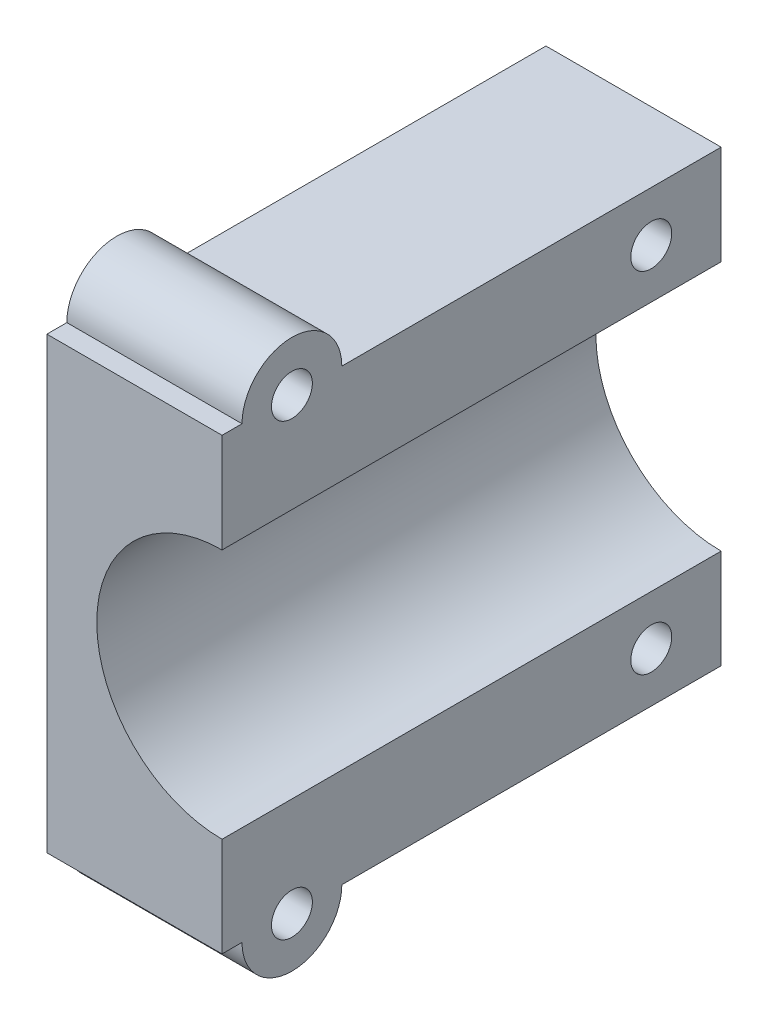
SolidWorks part; units mm, degrees
material "PLA"
ref_plane "Front Plane" through (0, 0, 0) normal (0, 0, 1) x (1, 0, 0)
ref_plane "Top Plane" through (0, 0, 0) normal (0, 1, 0) x (1, 0, 0)
ref_plane "Right Plane" through (0, 0, 0) normal (1, 0, 0) x (0, 0, -1)
sketch "Sketch1" plane through (0, 0, 0) normal (0, 0, 1) x (1, 0, 0)
  line L0 (-17.55, 22.5) -> (-17.55, 0)
  line L1 (55, 0) -> (-55, 0) construction
  line L2 (-17.55, 0) -> (17.55, 0)
  line L3 (17.55, 0) -> (17.55, 22.5)
  line L4 (-17.55, 22.5) -> (-12.55, 22.5)
  line L5 (17.55, 22.5) -> (12.55, 22.5)
  line L6 (0, -44.7868) -> (0, 44.7868) construction
  arc A0 (-12.55, 22.5) -> (12.55, 22.5) centre (0, 22.5) ccw
  dimension "D1" = 12.55
  dimension "D2" = 22.5
  dimension "D3" = 5
extrude "Boss-Extrude1" add sketch "Sketch1" along normal mid plane 50
sketch "Construct1" plane through (0, 0, 0) normal (0, 1, 0) x (1, 0, 0)
  line L0 (17.55, 0) -> (43.5308, -15) construction
  line L1 (-44.2539, 0) -> (44.2539, 0) construction
  line L2 (34.7676, -0.1782) -> (26.3131, -14.8218) construction
  line L3 (17.55, -25) -> (17.55, 25) construction
  point P6 (30.5404, -7.5)
  point P7 (30.5404, -7.5)
  dimension "D1" = 30
  dimension "D2" = 15
ref_plane "LegBuildPlane" through (26.1529, 0, 15.0994) normal (0.866, 0, 0.5) x (0.5, 0, -0.866)
sketch "Sketch5" plane through (26.1529, 0, 15.0994) normal (0.866, 0, 0.5) x (0.5, 0, -0.866)
  line L0 (-8.725, 22.5) -> (-3.775, 22.5)
  line L1 (21.325, 22.5) -> (26.275, 22.5)
  line L2 (17.2295, 0) -> (0.3205, 0) construction
  arc A0 (-3.775, 22.5) -> (21.325, 22.5) centre (8.775, 22.5) ccw
  arc A1 (-8.725, 22.5) -> (26.275, 22.5) centre (8.775, 22.5) ccw
  point P9 (8.775, 0)
  dimension "D1" = 17.5
  dimension "D2" = 12.55
  dimension "D3" = 22.5
  dimension "D4" = 0
extrude "Boss-Extrude2" add sketch "Sketch5" against normal up to surface and the other way blind 30 up to face at (17.55, 11.25, 0)
sketch "Sketch9" plane through (-17.55, 0, 0) normal (-1, 0, 0) x (0, 0, 1)
  line L2 (55, 0) -> (-55, 0) construction
  line L3 (-25, 22.5) -> (-25, 0) construction
  circle A0 centre (-18, 5) radius 2.05
  dimension "D1" = 4.1
  dimension "D2" = 5
  dimension "D3" = 7
extrude "Cut-Extrude3" cut sketch "Sketch9" against normal up to surface (35.1 mm away) up to face at (17.55, 12.0833, 0)
sketch "Construct2" plane through (0, 22.5, 0) normal (0, 1, 0) x (1, 0, 0)
  line L0 (20.1481, -15.9915) -> (32.6981, 5.7457) construction
  line L2 (50.2461, -33.3686) -> (17.55, -14.4915) construction
  line L3 (62.7961, -11.6314) -> (17.55, 14.4915) construction
  line L4 (17.55, 0) -> (26.4231, -5.1229) construction
  line L11 (-44.2539, 0) -> (44.2539, 0) construction
  dimension "D1" = 3
  dimension "D2" = 90
ref_plane "LegBuildPlane2" through (22.0356, 0, 12.7222) normal (0.866, 0, 0.5) x (0.5, 0, -0.866)
sketch "Sketch12" plane through (22.0356, 0, 12.7222) normal (0.866, 0, 0.5) x (0.5, 0, -0.866)
  line L0 (-3.775, 22.5) -> (21.325, 22.5)
  arc A0 (-3.775, 22.5) -> (21.325, 22.5) centre (8.775, 22.5) ccw
extrude "Boss-Extrude5" add sketch "Sketch12" against normal up to surface (17.4915 mm away) up to face at (17.55, 16.225, 0)
mirror "Mirror1" about plane through (17.55, 22.5, 25) normal (0, -1, 0) of "Boss-Extrude2", "Boss-Extrude1", "Cut-Extrude3", "Boss-Extrude5"
sketch "Sketch13" plane through (0, 0, 0) normal (0, 1, 0) x (1, 0, 0)
  line L0 (17.55, 0) -> (43.5308, -15) construction
  line L1 (47.7711, -37.6554) -> (65.2711, -7.3446) construction
  circle A0 centre (43.5308, -15) radius 1.55
  dimension "D2" = 3.1
  dimension "D1" = 15
extrude "Cut-Extrude4" cut sketch "Sketch13" along normal through all
sketch "Sketch16" plane through (0, 0, 0) normal (1, 0, 0) x (0, 0, -1)
  line L1 (25, 45) -> (-38, 45)
  line L2 (25, 45) -> (25, 0)
  line L3 (25, 0) -> (-38, 0)
  line L4 (-38, 45) -> (-38, 0)
  line L7 (55, 0) -> (-55, 0) construction
  line L8 (0, 44.2539) -> (0, -44.2539) construction
  dimension "D1" = 38
extrude "Cut-Extrude5" cut sketch "Sketch16" along normal up to surface (83.9453 mm away) up to face at (65.2711, 22.5, 7.3446)
sketch "Sketch17" plane through (-17.55, 0, 0) normal (-1, 0, 0) x (0, 0, 1)
  line L0 (55, 0) -> (-55, 0) construction
  line L1 (13, 0) -> (23, 0)
  arc A0 (13, 0) -> (23, 0) centre (18, 0) ccw
  circle A1 centre (-18, 5) radius 2.05 construction
  dimension "D2" = 5
  dimension "D1" = 36
extrude "Boss-Extrude6" add sketch "Sketch17" against normal blind 17.55
sketch "Sketch18" plane through (-17.55, 0, 0) normal (-1, 0, 0) x (0, 0, 1)
  circle A0 centre (18, 0) radius 2.05
  dimension "D1" = 4.1
extrude "Cut-Extrude6" cut sketch "Sketch18" against normal up to surface (17.55 mm away) up to face at (0, 5, -15.95)
ref_plane "HolePlane" through (0, 22.5, 0) normal (0, 1, 0) x (1, 0, 0)
mirror "Mirror2" about plane through (0, 22.5, 0) normal (0, 1, 0) of "Boss-Extrude6", "Cut-Extrude6"
equation "\"TubeDiam\"= 12.55"
equation "\"D1@Sketch1\"=\"TubeDiam\""
equation "\"D2@Sketch1\"=\"ClampHeight\""
equation "\"MountLength\"= 50"
equation "\"D1@Boss-Extrude1\"=\"MountLength\""
equation "\"MountHoleSize\"=3.1"
equation "\"LipWidth\"= 5"
equation "\"D3@Sketch1\"=\"LipWidth\""
equation "\"LegDiam\"=12.55"
equation "\"LegThickness\"= \"TubeDiam\" + 4.95"
equation "\"D1@Sketch5\"=\"LegThickness\""
equation "\"D2@Sketch5\"=\"TubeDiam\""
equation "\"ClampHeight\"= \"TubeDiam\" + 9.95"
equation "\"D3@Sketch5\"=\"ClampHeight\""
equation "\"HubHoleDist\"=7"
equation "\"HubHoleSize\"=4.1"
equation "\"D2@Sketch13\"=\"MountHoleSize\""
equation "\"D1@Sketch9\"=\"HubHoleSize\""
equation "\"D3@Sketch9\"=\"HubHoleDist\""
equation "\"D1@Sketch17\"=\"MountLength\" - 2 * \"HubHoleDist\""
equation "\"D1@Boss-Extrude6\"=\"TubeDiam\"+5"
equation "\"D1@Sketch18\"=\"HubHoleSize\""
